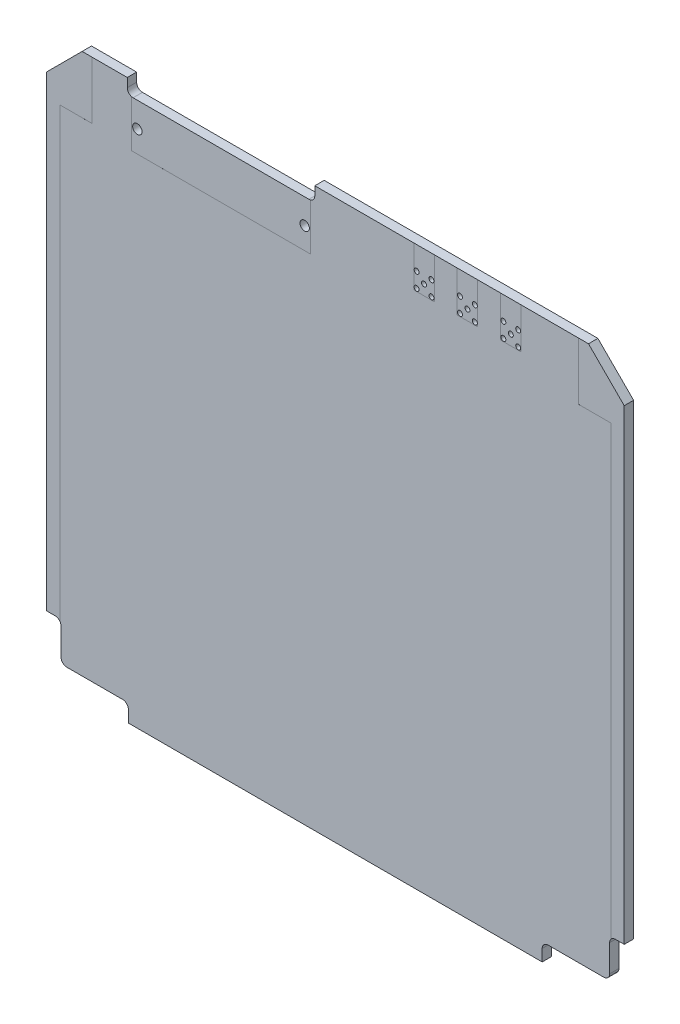
SolidWorks part; units mm, degrees
ref_plane "Front Plane" through (0, 0, 0) normal (0, 0, 1) x (1, 0, 0)
ref_plane "Top Plane" through (0, 0, 0) normal (0, 1, 0) x (1, 0, 0)
ref_plane "Right Plane" through (0, 0, 0) normal (1, 0, 0) x (0, 0, -1)
ref_plane "Plane4" through (0, 0, -0.0125) normal (0, 0, -1) x (-1, 0, 0)
sketch "Sketch1" plane through (0, 0, -0.0125) normal (0, 0, -1) x (-1, 0, 0)
  line L0 (35.3, -50) -> (35.3, -48)
  line L1 (36.3, -47) -> (45.8, -47)
  line L2 (46.8, -46) -> (46.8, -41.4)
  line L3 (47.8, -40.4) -> (49.3, -40.4)
  line L4 (49.3, -40.4) -> (49.3, 39.2)
  line L5 (49.3, 39.2) -> (43.2, 45.3)
  line L6 (43.2, 45.3) -> (35.5, 45.3)
  line L7 (35.5, 45.3) -> (35.5, 43.8)
  line L8 (34.5, 42.8) -> (4.5, 42.8)
  line L9 (3.5, 43.8) -> (3.5, 45.3)
  line L10 (3.5, 45.3) -> (-43.2, 45.3)
  line L11 (-43.2, 45.3) -> (-49.3, 39.2)
  line L12 (-49.3, 39.2) -> (-49.3, -40.4)
  line L13 (-49.3, -40.4) -> (-47.8, -40.4)
  line L14 (-46.8, -41.4) -> (-46.8, -46)
  line L15 (-45.8, -47) -> (-36.3, -47)
  line L16 (-35.3, -48) -> (-35.3, -50)
  line L17 (-35.3, -50) -> (35.3, -50)
  line L18 (0, -50) -> (0, 45.3) construction
  line L19 (19.5, 42.8) -> (19.5, 25.5258) construction
  line L20 (-13.87, 41.37) -> (-16.41, 38.83) construction
  line L21 (-21.27, 41.37) -> (-23.81, 38.83) construction
  line L22 (-28.67, 41.37) -> (-31.21, 38.83) construction
  arc A0 (35.3, -48) -> (36.3, -47) centre (36.3, -48) cw
  arc A1 (45.8, -47) -> (46.8, -46) centre (45.8, -46) ccw
  arc A2 (46.8, -41.4) -> (47.8, -40.4) centre (47.8, -41.4) cw
  arc A3 (35.5, 43.8) -> (34.5, 42.8) centre (34.5, 43.8) cw
  arc A4 (4.5, 42.8) -> (3.5, 43.8) centre (4.5, 43.8) cw
  arc A5 (-47.8, -40.4) -> (-46.8, -41.4) centre (-47.8, -41.4) cw
  arc A6 (-46.8, -46) -> (-45.8, -47) centre (-45.8, -46) ccw
  arc A7 (-36.3, -47) -> (-35.3, -48) centre (-36.3, -48) cw
  circle A8 centre (-21.27, 41.37) radius 0.425
  circle A9 centre (-23.81, 41.37) radius 0.425
  circle A10 centre (-22.54, 40.1) radius 0.425
  circle A11 centre (-13.87, 41.37) radius 0.425
  circle A12 centre (-23.81, 38.83) radius 0.425
  circle A13 centre (-16.41, 41.37) radius 0.425
  circle A14 centre (-15.14, 40.1) radius 0.425
  circle A15 centre (-21.27, 38.83) radius 0.425
  circle A16 centre (-28.67, 41.37) radius 0.425
  circle A17 centre (-31.21, 41.37) radius 0.425
  circle A18 centre (-16.41, 38.83) radius 0.425
  circle A19 centre (-29.94, 40.1) radius 0.425
  circle A20 centre (-31.21, 38.83) radius 0.425
  circle A21 centre (-28.67, 38.83) radius 0.425
  circle A22 centre (33.775, 38.54) radius 0.8
  circle A23 centre (5.225, 38.54) radius 0.8
  circle A24 centre (-13.87, 38.83) radius 0.425
  point P35 (-15.14, 40.1)
  dimension "D7" = 2.5
  dimension "D8" = 1.6
  dimension "D9" = 14.275
  dimension "D10" = 4.26
  dimension "D11" = 1
  dimension "D12" = 1
  dimension "D13" = 1
  dimension "D14" = 1
  dimension "D15" = 1
  dimension "D16" = 1
  dimension "D17" = 1
  dimension "D18" = 1
  dimension "D26" = 0.85
  dimension "D1" = 98.6
  dimension "D2" = 95.3
  dimension "D3" = 14
  dimension "D4" = 9.6
  dimension "D5" = 2.5
  dimension "D6" = 3
  dimension "D19" = 14
  dimension "D20" = 2.5
  dimension "D21" = 6.1
  dimension "D22" = 6.1
  dimension "D23" = 32
  dimension "D24" = 2.54
  dimension "D25" = 2.54
  dimension "D28" = 7.4
  dimension "D29" = 3.93
  dimension "D30" = 35.43
  dimension "D31" = 45
  dimension "D32" = 45
  dimension "D33" = 29.8
  dimension "D34" = 50
  dimension "D27" = 3
extrude "Boss-Extrude1" add sketch "Sketch1" against normal blind 1.6
sketch "thermalContacts_lower" plane through (0, 0, -0.0125) normal (0, 0, -1) x (-1, 0, 0)
  line L0 (47, 35.5) -> (47, -41.5) construction
  line L1 (41.5, 35.5) -> (41.5, 41.5) construction
  line L2 (41.5, 35.5) -> (47, 35.5) construction
  line L3 (47, 35.5) -> (47, -41.5)
  line L4 (41.5, 35.5) -> (41.5, 41.5)
  line L5 (41.5, 35.5) -> (47, 35.5)
  line L6 (-47, 35.5) -> (-47, -41.5) construction
  line L7 (-41.5, 35.5) -> (-47, 35.5) construction
  line L8 (-41.5, 35.5) -> (-41.5, 41.5) construction
  line L9 (-47, 35.5) -> (-47, -41.5)
  line L10 (-41.5, 35.5) -> (-47, 35.5)
  line L11 (-41.5, 35.5) -> (-41.5, 41.5)
  line L12 (-41.5, 41.5) -> (-41.5, 47) construction
  line L13 (-41.5, 41.5) -> (-49.5, 41.5) construction
  line L14 (-41.5, 41.5) -> (-41.5, 47)
  line L15 (-41.5, 41.5) -> (-49.5, 41.5) construction
  line L16 (41.5, 41.5) -> (41.5, 47) construction
  line L17 (41.5, 41.5) -> (49.5, 41.5) construction
  line L18 (41.5, 41.5) -> (41.5, 47)
  line L19 (41.5, 41.5) -> (49.5, 41.5) construction
  line L20 (47, -41.5) -> (59.8273, -41.5)
  line L21 (59.8273, -41.5) -> (59.8273, 47)
  line L22 (-56.1922, 47) -> (-41.5, 47)
  line L23 (41.5, 47) -> (59.8273, 47)
  line L24 (-56.1922, 47) -> (-56.1922, -41.5)
  line L25 (-47, -41.5) -> (-56.1922, -41.5)
sketch "thermalContacts_upper" plane through (0, 0, 1.5875) normal (0, 0, 1) x (1, 0, 0)
  line L3 (-47, 35.5) -> (-47, -41.5)
  line L4 (-41.5, 35.5) -> (-41.5, 41.5)
  line L5 (-41.5, 35.5) -> (-47, 35.5)
  line L9 (47, 35.5) -> (47, -41.5)
  line L10 (41.5, 35.5) -> (47, 35.5)
  line L11 (41.5, 35.5) -> (41.5, 41.5)
  line L14 (41.5, 41.5) -> (41.5, 47)
  line L15 (41.5, 41.5) -> (49.5, 41.5) construction
  line L18 (-41.5, 41.5) -> (-41.5, 47)
  line L19 (-41.5, 41.5) -> (-49.5, 41.5) construction
  line L20 (47, -41.5) -> (59.8273, -41.5)
  line L21 (59.8273, -41.5) -> (59.8273, 47)
  line L22 (59.8273, 47) -> (41.5, 47)
  line L23 (-41.5, 47) -> (-56.1922, 47)
  line L24 (-56.1922, 47) -> (-56.1922, -41.5)
  line L25 (-56.1922, -41.5) -> (-47, -41.5)
extrude "Cut-Extrude1" cut sketch "thermalContacts_lower" against normal blind 0.0001
extrude "Cut-Extrude2" cut sketch "thermalContacts_upper" against normal blind 0.0001
sketch "partFootprints" plane through (0, 0, 1.5875) normal (0, 0, 1) x (1, 0, 0)
  line L0 (-34.74, 34.84) -> (-34.74, 42.8292)
  line L1 (-4.26, 34.84) -> (-34.74, 34.84)
  line L2 (-41.5, 45.3) -> (-35.5, 45.3) construction
  line L3 (-36.1132, 45.3) -> (-39.5054, 45.3) construction
  line L4 (-4.26, 34.84) -> (-4.26, 42.8292)
  line L5 (-49.3, -40.4) -> (-49.3, 39.2) construction
  line L6 (13.39, 45.3) -> (13.39, 38.35)
  line L7 (13.39, 38.35) -> (16.89, 38.35)
  line L8 (16.89, 38.35) -> (16.89, 45.3)
  line L9 (16.89, 45.3) -> (13.39, 45.3)
  line L10 (20.79, 45.3) -> (20.79, 38.35)
  line L11 (20.79, 38.35) -> (24.29, 38.35)
  line L12 (24.29, 38.35) -> (24.29, 45.3)
  line L13 (24.29, 45.3) -> (20.79, 45.3)
  line L14 (28.19, 45.3) -> (28.19, 38.35)
  line L15 (28.19, 38.35) -> (31.69, 38.35)
  line L16 (31.69, 38.35) -> (31.69, 45.3)
  line L17 (31.69, 45.3) -> (28.19, 45.3)
  line L19 (14.12, 38.35) -> (16.16, 38.35) construction
  line L20 (-34.74, 42.8292) -> (-4.26, 42.8292)
  line L21 (-3.5, 45.3) -> (41.5, 45.3) construction
  line L22 (14.12, 38.35) -> (16.16, 38.35) construction
  line L23 (13.39, 41.85) -> (13.39, 38.35) construction
  line L24 (16.89, 41.85) -> (16.89, 38.35) construction
  line L25 (13.39, 41.85) -> (13.39, 38.35) construction
  line L26 (16.89, 41.85) -> (16.89, 38.35) construction
  arc A0 (-35.5, 43.8) -> (-34.5, 42.8) centre (-34.5, 43.8) ccw construction
  arc A1 (-4.5, 42.8) -> (-3.5, 43.8) centre (-4.5, 43.8) ccw construction
  point P18 (30.0301, 38.35)
  point P34 (13.39, 38.35)
  point P35 (13.39, 45.3)
  point P39 (24.29, 38.35)
  point P40 (20.79, 38.35)
  point P41 (20.79, 45.3)
  point P42 (31.69, 45.3)
  point P43 (31.69, 45.3)
  dimension "D1" = 10.46
  dimension "D2" = 14.56
  dimension "D3" = 30.48
  dimension "D7" = 7.4
  dimension "D6" = 3
extrude "Cut-Extrude3" cut sketch "partFootprints" against normal blind 0.0001
